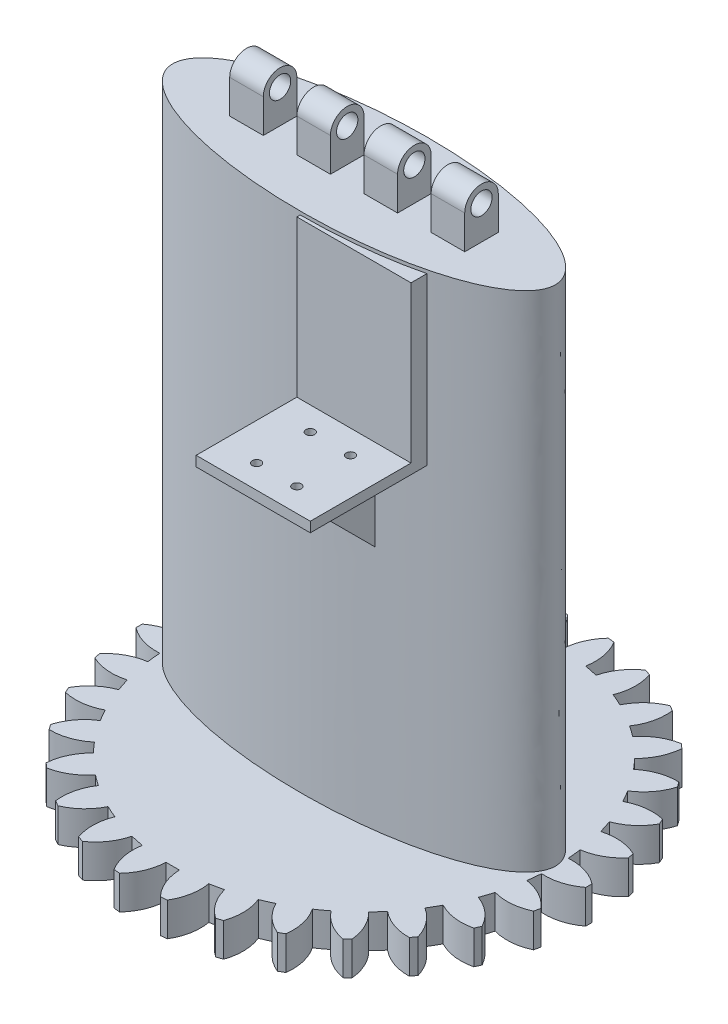
SolidWorks part; units mm, degrees
ref_plane "Plan de face" through (0, 0, 0) normal (0, 0, 1) x (1, 0, 0)
ref_plane "Plan de dessus" through (0, 0, 0) normal (0, 1, 0) x (1, 0, 0)
ref_plane "Plan de droite" through (0, 0, 0) normal (1, 0, 0) x (0, 0, -1)
sketch "Esquisse1" plane through (0, 0, 0) normal (0, 1, 0) x (1, 0, 0)
  ellipse E0 centre (0, 0) end of major axis (57, 0) minor radius 19
  dimension "D1" = 19
  dimension "D2" = 57
extrude "Boss.-Extru.1" add sketch "Esquisse1" along normal blind 150 contours E0
ref_plane "Plan1" through (0, 150, 0) normal (0, 1, 0) x (1, 0, 0)
sketch "Esquisse2" plane through (0, 150, 0) normal (0, 1, 0) x (1, 0, 0)
  line L1 (-35, 5) -> (-25, 5)
  line L2 (-35, 5) -> (-35, -5)
  line L3 (-35, -5) -> (-25, -5)
  line L4 (-25, 5) -> (-25, -5)
  point P4 (0, 0)
  point P5 (-25, 0)
  dimension "D1" = 10
  dimension "D2" = 25
extrude "Boss.-Extru.2" add sketch "Esquisse2" along normal blind 10
sketch "Esquisse3" plane through (-35, 0, 0) normal (-1, 0, 0) x (0, 0, 1)
  line L0 (-5, 160) -> (5, 160) construction
  circle A0 centre (0, 160) radius 5
  point P5 (0, 160)
extrude "Boss.-Extru.3" add sketch "Esquisse3" against normal up to surface (10 mm away) up to face at (-25, 155, 0)
hole_wizard "Dégagement M1.61" positions "Esquisse6" profile "Esquisse7" hole size "M1.6" standard "Ansi Metric" end condition through all
sketch "Esquisse6" plane through (-35, 0, 0) normal (-1, 0, 0) x (0, 0, 1)
  line L0 (-5, 150) -> (5, 150) construction
  point P0 (0, 160)
  point P16 (0, 150)
sketch "Esquisse7" plane through (-35, 160, 0) normal (0, 1, 0) x (0, 0, 1)
  line L0 (0, 0) -> (0, 32)
  line L1 (0, 32) -> (3.175, 32)
  line L2 (3.175, 32) -> (3.175, 0)
  line L5 (3.175, 0) -> (0, 0)
  line L11 (0, -6.35) -> (0, 107.95) construction
  dimension "Diamètre du perçage jusqu'au prochain" = 6.35
  dimension "Profondeur du perçage jusqu'au prochain" = 32
pattern_linear "Répétition linéaire1" count 4 spacing 20 along (1, 0, 0) of "Boss.-Extru.2", "Boss.-Extru.3", "Dégagement M1.61"
sketch "Esquisse8" plane through (0, 0, 0) normal (0, -1, 0) x (-1, 0, 0)
  circle A1 centre (0, 0) radius 67
  dimension "D1" = 134
extrude "Boss.-Extru.4" add sketch "Esquisse8" along normal blind 10
sketch "Esquisse9" plane through (0, -10, 0) normal (0, -1, 0) x (1, 0, 0)
  line L0 (0, -73.7) -> (0, 73.7) construction
  line L1 (0, 67) -> (0, 0) construction
  line L2 (0, 0) -> (-1.9893, 56.9653) construction
  line L3 (-8.7107, 68.952) -> (0, 0) construction
  line L4 (-5.6869, 69.2669) -> (0, 53.6422) construction
  circle A0 centre (0, 0) radius 67
  circle A1 centre (0, 0) radius 57
  circle A2 centre (0, 0) radius 67 construction
  arc A3 (-8.7107, 68.952) -> (-1.9893, 56.9653) centre (-16.98, 56.4372) cw
  arc A4 (-8.7107, 68.952) -> (8.7107, 68.952) centre (0, 0) cw
  arc A6 (8.7107, 68.952) -> (1.9893, 56.9653) centre (16.98, 56.4372) ccw
  dimension "D1" = 10
  dimension "D5" = 2.5
  dimension "D6" = 15
  dimension "D2" = 2
  dimension "D3" = 7.2
  dimension "D4" = 20
extrude "Enlèv. mat.-Extru.6" cut sketch "Esquisse9" against normal through all contours A6 A0 A3 A1 | A6 A4 A3 A0 region at (0, -10, 62.9516) region at (0, -10, 68.191)
pattern_circular "Répétition circulaire1" count 30 over 360 about axis through (0, -10, 0) along (0, -1, 0) of "Enlèv. mat.-Extru.6"
sketch "Esquisse10" plane through (0, -10, 0) normal (0, -1, 0) x (1, 0, 0)
  line L0 (-2, -2.4659) -> (2, -2.4659)
  circle A0 centre (0, 0) radius 3.175
  dimension "D1" = 6.35
  dimension "D2" = 4
extrude "Enlèv. mat.-Extru.7" cut sketch "Esquisse10" against normal blind 101.6 contours L0 A0 region at (0, -10, 0.1794)
sketch "Esquisse11" plane through (0, 0, 0) normal (0, 0, 1) x (1, 0, 0)
  line L0 (20.9, 150) -> (-20.9, 150) construction
  line L1 (0, 149) -> (34, 149)
  line L2 (0, 149) -> (0, 102.5)
  line L3 (0, 102.5) -> (34, 102.5)
  line L4 (34, 149) -> (34, 102.5)
  dimension "D1" = 34
  dimension "D2" = 46.5
  dimension "D3" = 1
extrude "Boss.-Extru.5" add sketch "Esquisse11" along normal blind 20
sketch "Esquisse12" plane through (0, 0, 0) normal (0, 0, 1) x (1, 0, 0)
  line L1 (0, 102.5) -> (34, 102.5)
  line L2 (0, 102.5) -> (0, 99.5)
  line L3 (0, 99.5) -> (34, 99.5)
  line L4 (34, 102.5) -> (34, 99.5)
  line L6 (34, 102.5) -> (34, 149) construction
  point P7 (0, 84.5245)
  dimension "D1" = 3
extrude "Boss.-Extru.6" add sketch "Esquisse12" along normal blind 50
ref_plane "Plan3" through (17, 0, 0) normal (-1, 0, 0) x (0, 0, 1)
sketch "Esquisse14" plane through (17, 0, 0) normal (1, 0, 0) x (0, 0, -1)
  line L0 (-44, 99.5) -> (-19, 74.5)
  line L5 (-50, 99.5) -> (-19, 99.5) construction
  line L6 (-50, 99.5) -> (-50, 102.5) construction
  line L7 (-50, 99.5) -> (-19, 99.5) construction
  line L12 (-19, 99.5) -> (-19, 0) construction
  point P4 (-19, 72.6814)
  point P7 (-19.4951, 0)
  point P9 (-19, 77.535)
  dimension "D1" = 45
  dimension "D2" = 6
rib "Nervure13" sketch "Esquisse14" sketch "Esquisse14" thickness 8 extrusion direction parallel to sketch draft on no parameters "D1"=8
hole_wizard "Dégagement M21" positions "Esquisse16" profile "Esquisse17" hole size "M2" standard "Ansi Metric" end condition up to next
sketch "Esquisse16" plane through (0, 102.5, 0) normal (0, 1, 0) x (1, 0, 0)
  line L0 (0, -50) -> (0, -20) construction
  line L1 (0, -35) -> (34, -35) construction
  line L2 (34, -50) -> (34, -20) construction
  point P0 (11, -43)
  point P2 (23, -43)
  point P4 (23, -27)
  point P6 (11, -27)
  point P23 (11, -43)
  point P24 (0, 0)
  dimension "D1" = 12
  dimension "D2" = 11
  dimension "D3" = 16
  dimension "D4" = 8
sketch "Esquisse17" plane through (11, 102.5, 43) normal (1, 0, 0) x (0, 0, 1)
  line L0 (0, 0) -> (0, 3)
  line L1 (0, 3) -> (1.3, 3)
  line L2 (1.3, 3) -> (1.3, 0)
  line L5 (1.3, 0) -> (0, 0)
  line L11 (0, -6.35) -> (0, 107.95) construction
  dimension "Diamètre du perçage jusqu'au prochain" = 2.6
  dimension "Profondeur du perçage jusqu'au prochain" = 3
equation "\"Nombre de dents\"= 20"
